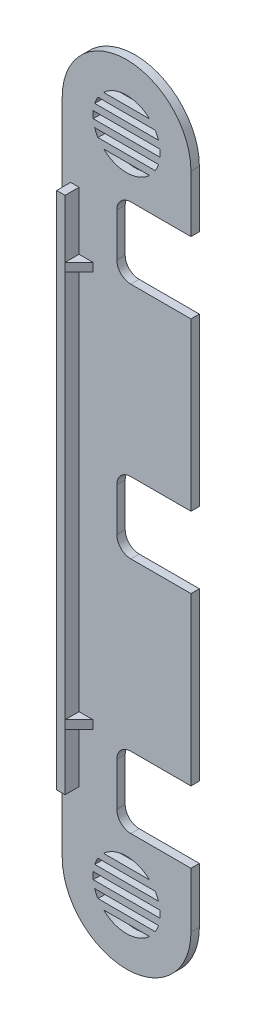
SolidWorks part; units mm, degrees
ref_plane "Front Plane" through (0, 0, 0) normal (0, 0, 1) x (1, 0, 0)
ref_plane "Top Plane" through (0, 0, 0) normal (0, 1, 0) x (1, 0, 0)
ref_plane "Right Plane" through (0, 0, 0) normal (1, 0, 0) x (0, 0, -1)
sketch "Sketch1" plane through (0, 0, 0) normal (0, 0, 1) x (1, 0, 0)
  line L0 (-23.5, 139.9624) -> (-23.5, 114.5)
  line L1 (-43, 160.25) -> (-43, -75.25)
  line L2 (3, 160.25) -> (3, 139.9624)
  line L4 (-23.5, -30.0376) -> (3, -30.0376)
  line L6 (-23.5, -55.5) -> (3, -55.5)
  line L8 (-23.5, 54.9624) -> (3, 54.9624)
  line L10 (-23.5, 29.5) -> (3, 29.5)
  line L12 (-23.5, 139.9624) -> (3, 139.9624)
  line L14 (-23.5, 114.5) -> (3, 114.5)
  line L16 (-23.5, 54.9624) -> (-23.5, 29.5)
  line L17 (-23.5, -30.0376) -> (-23.5, -55.5)
  line L24 (3, -55.5) -> (3, -75.25)
  line L25 (3, 29.5) -> (3, -30.0376)
  line L26 (3, 114.5) -> (3, 54.9624)
  arc A2 (3, 160.25) -> (-43, 160.25) centre (-20, 160.25) ccw
  arc A3 (-43, -75.25) -> (3, -75.25) centre (-20, -75.25) ccw
extrude "Boss-Extrude1" add sketch "Sketch1" along normal blind 3
fillet "Fillet1" radius 5 6 edges at (-23.5, 139.9624, 1.5) (-23.5, 114.5, 1.5) (-23.5, 54.9624, 1.5) (-23.5, 29.5, 1.5) (-23.5, -55.5, 1.5) (-23.5, -30.0376, 1.5)
sketch "Sketch2" plane through (0, 0, 3) normal (0, 0, 1) x (1, 0, 0)
  line L0 (-20, 183.25) -> (-20, -98.25) construction
  line L1 (-20, 42.5) -> (-43, 42.5) construction
  line L2 (-43, 160.25) -> (-43, -75.25) construction
  line L3 (3, 84.7312) -> (-20, 84.7312) construction
  line L4 (3, 54.9624) -> (3, 114.5) construction
  line L5 (-32, 160.25) -> (-8, 160.25) construction
  line L6 (-31.9347, 161.5) -> (-8.0653, 161.5)
  line L7 (-31.399, 164) -> (-8.601, 164)
  line L8 (-30.2439, 166.5) -> (-9.7561, 166.5)
  line L9 (-28.212, 169) -> (-11.788, 169)
  line L10 (-31.9347, 159) -> (-8.0653, 159)
  line L11 (-28.212, 151.5) -> (-11.788, 151.5)
  line L12 (-30.2439, 154) -> (-9.7561, 154)
  line L13 (-31.399, 156.5) -> (-8.601, 156.5)
  line L14 (-32, -75.25) -> (-8, -75.25) construction
  line L15 (-31.399, -71.5) -> (-8.601, -71.5)
  line L16 (-30.2439, -69) -> (-9.7561, -69)
  line L17 (-28.212, -66.5) -> (-11.788, -66.5)
  line L18 (-31.9347, -74) -> (-8.0653, -74)
  line L19 (-28.212, -84) -> (-11.788, -84)
  line L20 (-30.2439, -81.5) -> (-9.7561, -81.5)
  line L21 (-31.399, -79) -> (-8.601, -79)
  line L22 (-31.9347, -76.5) -> (-8.0653, -76.5)
  line L47 (3, 0.2688) -> (-20, 0.2688) construction
  arc A0 (3, 160.25) -> (-43, 160.25) centre (-20, 160.25) ccw construction
  arc A1 (-43, -75.25) -> (3, -75.25) centre (-20, -75.25) ccw construction
  arc A2 (-30.2439, 166.5) -> (-31.399, 164) centre (-20, 160.25) ccw
  arc A3 (-11.788, 169) -> (-28.212, 169) centre (-20, 160.25) ccw
  arc A4 (-8.601, 164) -> (-9.7561, 166.5) centre (-20, 160.25) ccw
  arc A5 (-31.9347, 161.5) -> (-31.9347, 159) centre (-20, 160.25) ccw
  arc A6 (-31.399, 156.5) -> (-30.2439, 154) centre (-20, 160.25) ccw
  arc A7 (-8.0653, 159) -> (-8.0653, 161.5) centre (-20, 160.25) ccw
  arc A8 (-9.7561, 154) -> (-8.601, 156.5) centre (-20, 160.25) ccw
  arc A9 (-28.212, 151.5) -> (-11.788, 151.5) centre (-20, 160.25) ccw
  arc A10 (-28.212, -66.5) -> (-11.788, -66.5) centre (-20, -75.25) cw
  arc A11 (-9.7561, -69) -> (-8.601, -71.5) centre (-20, -75.25) cw
  arc A12 (-8.0653, -74) -> (-8.0653, -76.5) centre (-20, -75.25) cw
  arc A13 (-31.399, -71.5) -> (-30.2439, -69) centre (-20, -75.25) cw
  arc A14 (-31.9347, -76.5) -> (-31.9347, -74) centre (-20, -75.25) cw
  arc A15 (-8.601, -79) -> (-9.7561, -81.5) centre (-20, -75.25) cw
  arc A16 (-11.788, -84) -> (-28.212, -84) centre (-20, -75.25) cw
  arc A17 (-30.2439, -81.5) -> (-31.399, -79) centre (-20, -75.25) cw
  dimension "D1" = 1.25
  dimension "D2" = 2.5
  dimension "D3" = 2.5
  dimension "D4" = 2.5
extrude "Cut-Extrude1" cut sketch "Sketch2" against normal up to surface (3 mm away) up to face at (-14.5551, 42.2801, 0)
sketch "Sketch3" plane through (0, 0, 3) normal (0, 0, 1) x (1, 0, 0)
  line L1 (-40, -50.25) -> (-37, -50.25)
  line L2 (-40, -50.25) -> (-40, 135.25)
  line L3 (-40, 135.25) -> (-37, 135.25)
  line L4 (-37, -50.25) -> (-37, 135.25)
  line L6 (-43, 148.0073) -> (-43, -63.0073) construction
  arc A0 (3, 160.25) -> (-43, 160.25) centre (-20, 160.25) ccw construction
  arc A1 (-43, -75.25) -> (-3.6462, -91.4226) centre (-20, -75.25) ccw construction
  dimension "D3" = 25
  dimension "D1" = 3
  dimension "D2" = 25
  dimension "D4" = 3
extrude "Boss-Extrude2" add sketch "Sketch3" along normal blind 5
sketch "Sketch4" plane through (0, -30.0376, 0) normal (0, -1, 0) x (1, 0, 0)
  line L0 (-37, 8) -> (-37, 3) construction
  line L1 (-37, 8) -> (-37, 3)
  line L2 (-37, 3) -> (-32, 3)
  line L3 (3, 3) -> (-43, 3) construction
  line L4 (-32, 3) -> (-37, 8)
  dimension "D1" = 45
extrude "Boss-Extrude3" add sketch "Sketch4" against normal blind 3
sketch "Sketch5" plane through (0, 114.5, 0) normal (0, 1, 0) x (1, 0, 0)
  line L3 (-37, -8) -> (-32, -3)
  line L4 (-37, -3) -> (-37, -8)
  line L5 (-32, -3) -> (-37, -3)
  line L6 (-37, -8) -> (-32, -3)
  line L7 (-37, -3) -> (-37, -8)
  line L8 (-32, -3) -> (-37, -3)
  dimension "D1" = 0
extrude "Boss-Extrude4" add sketch "Sketch5" against normal blind 3
